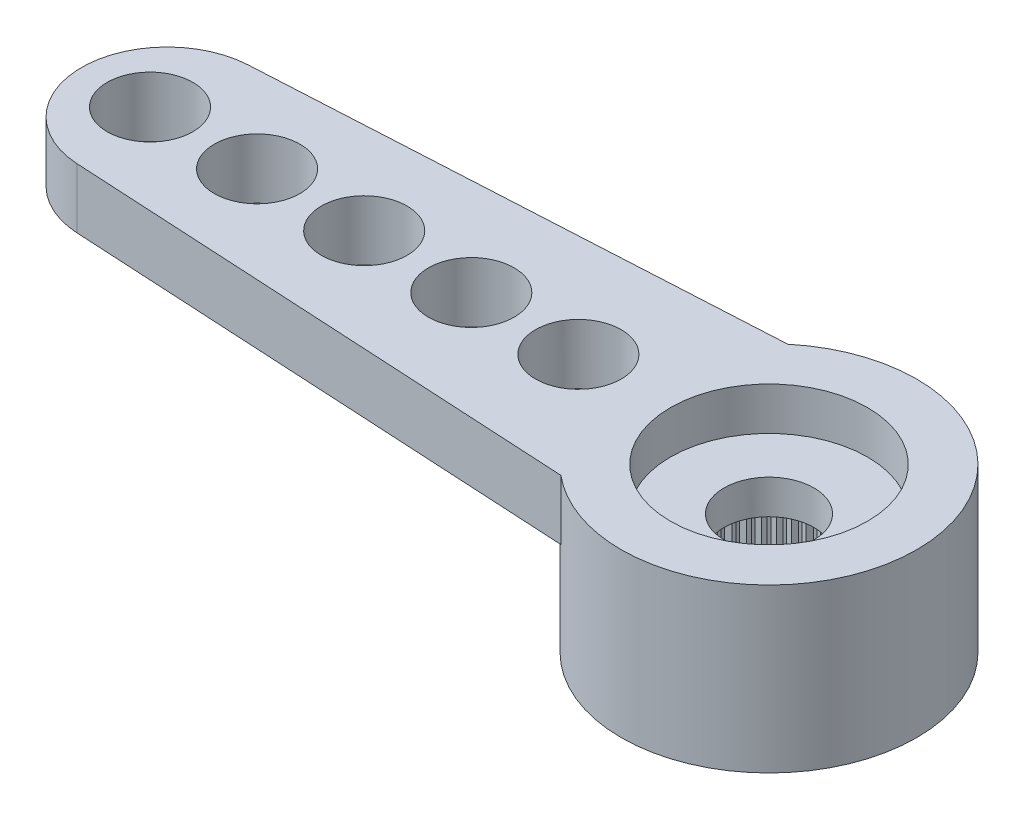
SolidWorks part; units mm, degrees
material "PVC Rígido"
ref_plane "Plano frontal" through (0, 0, 0) normal (0, 0, 1) x (1, 0, 0)
ref_plane "Plano superior" through (0, 0, 0) normal (0, 1, 0) x (1, 0, 0)
ref_plane "Plano direito" through (0, 0, 0) normal (1, 0, 0) x (0, 0, -1)
sketch "Esboço1" plane through (0, 0, 0) normal (0, 1, 0) x (1, 0, 0)
  line L0 (0, 0) -> (-14.05, 0) construction
  line L1 (-14.1591, 1.997) -> (-2.2091, 2.65)
  line L2 (-2.2091, -2.65) -> (-14.1591, -1.997)
  arc A0 (-2.2091, -2.65) -> (-2.2091, 2.65) centre (0, 0) ccw
  arc A1 (-14.1591, 1.997) -> (-14.1591, -1.997) centre (-14.05, 0) ccw
  dimension "D1" = 6.9
  dimension "D2" = 4
  dimension "D3" = 19.5
  dimension "D4" = 5.3
extrude "Ressalto-extrusão1" add sketch "Esboço1" against normal blind 1.4
sketch "Esboço2" plane through (0, -1.4, 0) normal (0, -1, 0) x (1, 0, 0)
  arc A0 (-2.2091, -2.65) -> (-2.2091, 2.65) centre (0, 0) ccw construction
  circle A1 centre (0, 0) radius 3.45
extrude "Ressalto-extrusão2" add sketch "Esboço2" along normal offset from surface (2.4 mm away) 3.8 up to face at (-7.242, 0, 0)
hole_wizard "Furo4" positions "Esboço9" profile "Esboço10" legacy end condition through all
sketch "Esboço9" plane through (0, 0, 0) normal (0, 1, 0) x (1, 0, 0)
  line L1 (-14.45, 0) -> (0, 0) construction
  arc A2 (-14.1591, 1.997) -> (-14.1591, -1.997) centre (-14.05, 0) ccw construction
  point P0 (-14.45, 0)
  point P19 (-16.05, 0)
  dimension "D1" = 1.6
sketch "Esboço10" plane through (-14.45, 0, 0) normal (1, 0, 0) x (0, 0, 1)
  line L0 (0, 0) -> (0, 3.8)
  line L1 (0, 3.8) -> (1, 3.8)
  line L2 (1, 3.8) -> (1, 0)
  line L3 (1, 0) -> (0, 0)
  line L4 (0, 110) -> (0, -10) construction
  dimension "Diameter" = 2
  dimension "Depth" = 3.8
pattern_linear "Padrão linear1" count 5 spacing 2.5 along (1, 0, 0) of "Furo4"
hole_wizard "Furo1" positions "Esboço3" profile "Esboço4" legacy
sketch "Esboço3" plane through (0, -3.8, 0) normal (0, -1, 0) x (-1, 0, 0)
  point P0 (0, 0)
sketch "Esboço4" plane through (0, -3.8, 0) normal (1, 0, 0) x (0, 0, -1)
  line L0 (0, 0) -> (0, 2)
  line L1 (0, 2) -> (2.475, 2)
  line L2 (2.475, 2) -> (2.475, 0)
  line L3 (2.475, 0) -> (0, 0)
  line L4 (0, 110) -> (0, -10) construction
  dimension "Diameter" = 4.95
  dimension "Depth" = 2
hole_wizard "Furo2" positions "Esboço5" profile "Esboço6" legacy
sketch "Esboço5" plane through (0, 0, 0) normal (0, 1, 0) x (1, 0, 0)
  point P0 (0, 0)
sketch "Esboço6" plane through (0, 0, 0) normal (1, 0, 0) x (0, 0, 1)
  line L0 (0, 0) -> (0, 1)
  line L1 (0, 1) -> (2.3, 1)
  line L2 (2.3, 1) -> (2.3, 0)
  line L3 (2.3, 0) -> (0, 0)
  line L4 (0, 110) -> (0, -10) construction
  dimension "Diameter" = 4.6
  dimension "Depth" = 1
hole_wizard "Furo3" positions "Esboço7" profile "Esboço8" legacy end condition through all
sketch "Esboço7" plane through (0, 0, 0) normal (0, 1, 0) x (1, 0, 0)
  point P0 (0, 0)
sketch "Esboço8" plane through (0, 0, 0) normal (1, 0, 0) x (0, 0, 1)
  line L0 (0, 0) -> (0, 3.8)
  line L1 (0, 3.8) -> (1.05, 3.8)
  line L2 (1.05, 3.8) -> (1.05, 0)
  line L3 (1.05, 0) -> (0, 0)
  line L4 (0, 110) -> (0, -10) construction
  dimension "Diameter" = 2.1
  dimension "Depth" = 3.8
sketch "Esboço11" plane through (0, -3.8, 0) normal (0, -1, 0) x (1, 0, 0)
  line L0 (-0.0981, 2.4731) -> (0, 2.375)
  line L1 (0, 2.375) -> (0.0981, 2.4731)
  line L2 (0, 0) -> (0, 2.475) construction
  circle A0 centre (0, 0) radius 2.375 construction
  circle A1 centre (0, 0) radius 2.475
  arc A2 (0.0981, 2.4731) -> (-0.0981, 2.4731) centre (0, 0) ccw
  dimension "D3" = 4.75
  dimension "D2" = 0.1
  dimension "D1" = 0
extrude "Ressalto-extrusão3" add sketch "Esboço11" against normal up to surface (2 mm away) up to face at (0, -1.8, 1.05)
pattern_circular "PadrãoCircular1" count 60 over 360 about axis through (0, -1.4, 0) along (0, 1, 0) of "Ressalto-extrusão3"
